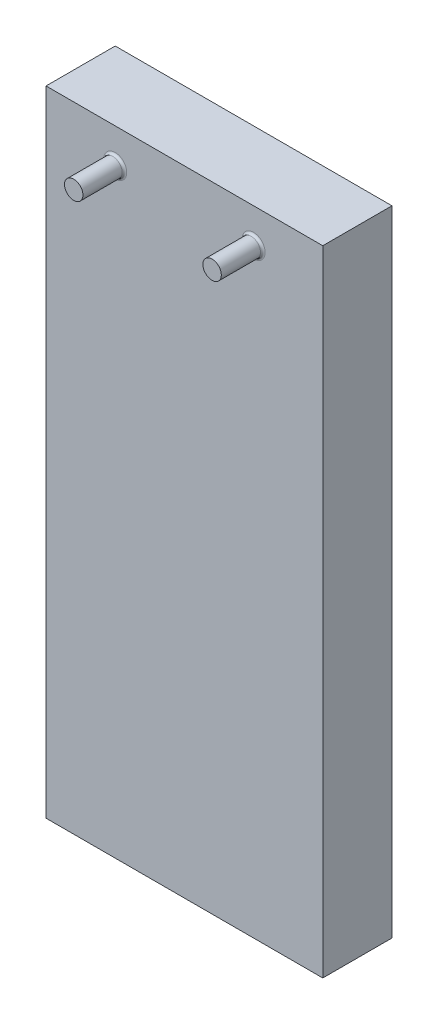
SolidWorks part; units mm, degrees
ref_plane "Front Plane" through (0, 0, 0) normal (0, 0, 1) x (1, 0, 0)
ref_plane "Top Plane" through (0, 0, 0) normal (0, 1, 0) x (1, 0, 0)
ref_plane "Right Plane" through (0, 0, 0) normal (1, 0, 0) x (0, 0, -1)
sketch "Sketch1" plane through (0, 0, 0) normal (0, 1, 0) x (1, 0, 0)
  line L1 (-60, -15) -> (60, -15)
  line L2 (-60, -15) -> (-60, 15)
  line L3 (-60, 15) -> (60, 15)
  line L4 (60, -15) -> (60, 15)
  line L5 (-60, -15) -> (60, 15) construction
  line L6 (-60, 15) -> (60, -15) construction
  point P0 (0, 0)
  dimension "D1" = 120
  dimension "D2" = 30
extrude "Boss-Extrude1" add sketch "Sketch1" along normal blind 275
sketch "Sketch2" plane through (0, 0, 15) normal (0, 0, 1) x (1, 0, 0)
  line L0 (-60, 245) -> (60, 245)
  line L1 (-60, 275) -> (-60, 0) construction
  line L2 (60, 275) -> (60, 0) construction
  line L3 (-60, 275) -> (60, 275) construction
  line L4 (-60, 245) -> (-60, 275)
  line L5 (-60, 260) -> (60, 260) construction
  circle A2 centre (-30, 260) radius 4
  circle A3 centre (30, 260) radius 4
  dimension "D4" = 8
  dimension "D1" = 30
  dimension "D2" = 30
  dimension "D3" = 30
extrude "Boss-Extrude2" add sketch "Sketch2" along normal blind 18 contours L5 A3 | A3 L5 | L5 A2 | A2 L5 region at (-30, 261.6977, 15) region at (30, 261.6977, 15) region at (30, 258.3023, 15) region at (-30, 258.3023, 15)
fillet "Fillet1" radius 1 2 edges at (26, 260, 15) (-34, 260, 15)
equation "\"PCWidth\"= 242mm'Distance of longest part parallel to GPU(ussually GPU)"
equation "\"PCLength\"= 316mm'Length across I/O from PS to GPU"
equation "\"PCHeight\"= 178mm'Tallest point with mobo laying flat"
equation "\"WallThickness\"= 9mm'Thickness of each outer tank wall"
equation "\"ThermoBarrierThickness\"= 3mm'Thickness of barrier between hot side and cold side"
equation "\"HotSideGap\"= 25mm'Space in the hot side for a pump"
equation "\"PCClearance\"= 30mm'Clearance from top of tank to top of PC"
equation "\"RadiatorHeight\"= 275mm'Final Height from ground of radiators"
equation "\"D1@Boss-Extrude1\"=\"RadiatorHeight\""
